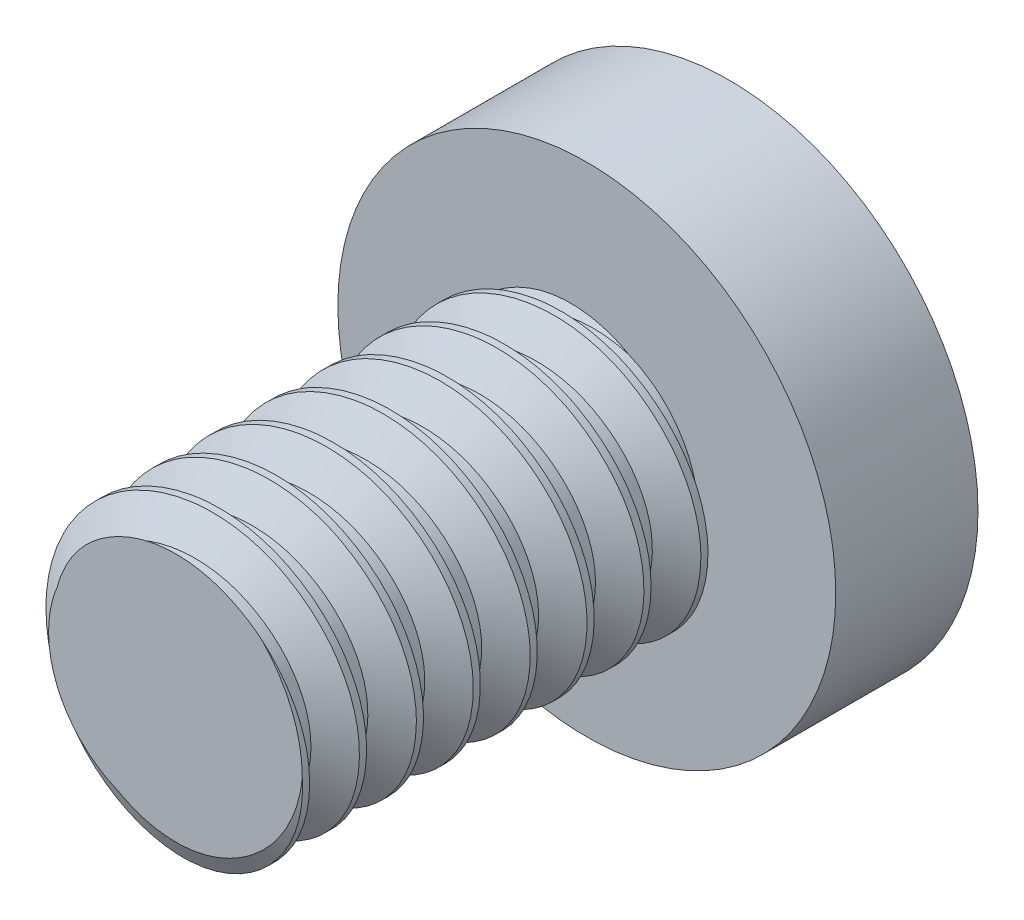
SolidWorks part; units mm, degrees
ref_plane "前视基准面" through (0, 0, 0) normal (0, 0, 1) x (1, 0, 0)
ref_plane "上视基准面" through (0, 0, 0) normal (0, 1, 0) x (1, 0, 0)
ref_plane "右视基准面" through (0, 0, 0) normal (1, 0, 0) x (0, 0, -1)
other "Configuration Table"
sketch "草图1" plane through (0, 0, 0) normal (0, 0, 1) x (1, 0, 0)
  line L1 (0.4319, 0.7506) -> (-0.4341, 0.7494)
  line L2 (-0.4341, 0.7494) -> (-0.866, -0.0012)
  line L3 (-0.866, -0.0012) -> (-0.4319, -0.7506)
  line L4 (-0.4319, -0.7506) -> (0.4341, -0.7494)
  line L5 (0.4341, -0.7494) -> (0.866, 0.0012)
  line L6 (0.866, 0.0012) -> (0.4319, 0.7506)
  circle A0 centre (0, 0) radius 0.75 construction
  circle A1 centre (0, 0) radius 1.75
  dimension "D2" = 3.5
  dimension "D1" = 1.5
extrude "凸台-拉伸1" add sketch "草图1" along normal blind 0.8
sketch "草图2" plane through (0, 0, 0.8) normal (0, 0, 1) x (1, 0, 0)
  circle A1 centre (0, 0) radius 1.75
  circle A2 centre (0, 0) radius 1.75
  dimension "D1" = 0
extrude "凸台-拉伸2" add sketch "草图2" along normal blind 0.2
sketch "草图3" plane through (0, 0, 1) normal (0, 0, 1) x (1, 0, 0)
  circle A0 centre (0, 0) radius 1
  dimension "D1" = 2
extrude "凸台-拉伸3" add sketch "草图3" along normal blind 3
thread "螺纹线3" pitch 0.4 start angle 0, offset 1, length 10, pitch 0.4, diameter 2
ref_plane "基准面2" through (1, 0, 0) normal (0, -1, 0) x (1, 0, 0)
sketch "螺纹线轮廓2" plane through (1, 0, 0) normal (0, -1, 0) x (1, 0, 0)
  line L0 (0, 0) -> (0, 0.4) construction
  line L11 (0, 0) -> (0, 0.35)
  line L12 (0, 0.35) -> (-0.2165, 0.225)
  line L13 (-0.2165, 0.225) -> (-0.2165, 0.125)
  line L15 (-0.2165, 0.125) -> (0, 0)
  line L17 (-0.2165, 0.175) -> (0, 0.175) construction
  point P2 (0, 0)
  dimension "Pitch" = 0.4
  dimension "Profile_Angle" = 60
  dimension "Profile_Land" = 0.1
  dimension "Profile_Height" = 0.2165
